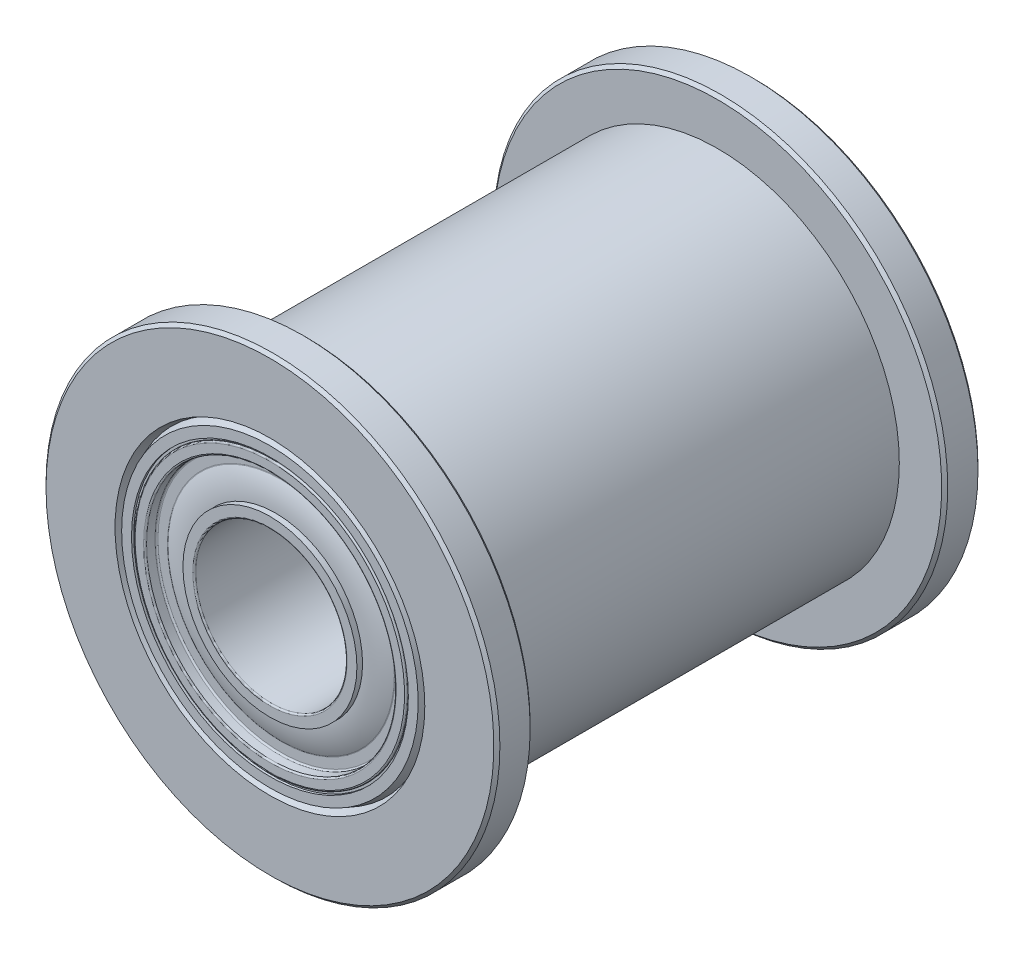
SolidWorks part; units mm, degrees
ref_plane "Front" through (0, 0, 0) normal (0, 0, 1) x (1, 0, 0)
ref_plane "Top" through (0, 0, 0) normal (0, 1, 0) x (1, 0, 0)
ref_plane "Right" through (0, 0, 0) normal (1, 0, 0) x (0, 0, -1)
sketch "Sketch1" plane through (0, 0, 0) normal (1, 0, 0) x (0, 0, -1)
  line L0 (-8, 0) -> (8, 0) construction
  line L1 (8, 7.5) -> (8, -7.5) construction
  line L2 (8, 7.5) -> (6.8, 7.5) construction
  line L3 (8, 2.5) -> (8, -2.5) construction
  line L4 (8, 6) -> (8, -6) construction
  line L5 (6, 0) -> (-6, 0) construction
  line L6 (6.8, 7.5) -> (6.8, 6) construction
  dimension "D3" = 1.2
  dimension "Width" = 16
  dimension "OD" = 15
  dimension "ID" = 5
  dimension "Diameter" = 12
  dimension "Max Belt Width" = 12
  dimension "Groove Depth" = 1.5
sketch "Sketch2" plane through (0, 0, 0) normal (1, 0, 0) x (0, 0, -1)
  line L0 (8, 2.5) -> (0, 2.5)
  line L1 (8, 2.5) -> (8, 2.875)
  line L2 (8, 7.5) -> (8, -7.5) construction
  line L3 (8, 2.875) -> (7.625, 2.875) construction
  line L4 (7.8125, 4.125) -> (7.8125, 2.875) construction
  line L5 (8, 4.5) -> (0, 4.5)
  line L6 (7.625, 3.75) -> (7.625, 4.125)
  line L7 (8, 4.5) -> (8, 4.125)
  line L8 (8, 4.125) -> (7.625, 4.125)
  line L9 (7.625, 4.125) -> (7.625, 2.875) construction
  line L10 (0, 4.5) -> (0, 2.5)
  line L11 (7.8125, 2.875) -> (8, 2.875)
  arc A0 (7.625, 3.75) -> (7.8125, 2.875) centre (5.6771, 2.875) cw
  dimension "D1" = 1.5
  dimension "D2" = 0.375
revolve "Revolve1" add sketch "Sketch2" angle 360 about L0
mirror "Mirror1" about plane through (0, 0, 0) normal (0, 0, 1) of bodies 108
sketch "Sketch3" plane through (0, 0, 0) normal (1, 0, 0) x (0, 0, -1)
  line L0 (6.8, 7.5) -> (8, 7.5)
  line L1 (8, 7.5) -> (8, 5.1184)
  line L2 (8, 7.5) -> (8, -7.5) construction
  line L3 (8, 5.1184) -> (7.7, 5.0092)
  line L4 (7.7, 5.0092) -> (8, 4.9)
  line L5 (8, 4.9) -> (8, 4.575)
  line L6 (7.925, 4.5) -> (7.925, 4.575)
  line L7 (8, 4.5) -> (-8, 4.5) construction
  line L8 (7.925, 4.575) -> (8, 4.575)
  line L9 (6.8, 7.5) -> (6.8, 6)
  line L10 (6.8, 6) -> (-6.8, 6)
  line L11 (0, 6) -> (0, 4.5) construction
  line L12 (-7.925, 4.5) -> (7.925, 4.5)
  line L13 (-6.8, 7.5) -> (-6.8, 6)
  line L14 (-7.925, 4.575) -> (-8, 4.575)
  line L15 (-7.925, 4.5) -> (-7.925, 4.575)
  line L16 (-8, 4.9) -> (-8, 4.575)
  line L17 (-7.7, 5.0092) -> (-8, 4.9)
  line L18 (-8, 5.1184) -> (-7.7, 5.0092)
  line L19 (-8, 7.5) -> (-8, 5.1184)
  line L20 (-6.8, 7.5) -> (-8, 7.5)
  line L21 (7.7, 5.0092) -> (8, 5.0092) construction
  line L22 (7.85, 5.0092) -> (7.85, 4.5) construction
  dimension "D1" = 40
  dimension "D2" = 0.3
  dimension "D3" = 0.075
  dimension "D4" = 0.4
revolve "Revolve2" add sketch "Sketch3" angle 360 about L0
sketch "Sketch4" plane through (0, 0, 0) normal (0, 0, 1) x (1, 0, 0)
  line L0 (-0.6, 6) -> (0.6, 6)
  line L1 (-0.6, 6) -> (-0.6, 5.4) construction
  line L2 (-0.6, 5.4) -> (0.6, 5.4) construction
  line L3 (0.6, 5.4) -> (0.6, 6) construction
  line L4 (0, 6) -> (0, 5.4) construction
  arc A0 (0.6, 6) -> (-0.6, 6) centre (0, 6) cw
  dimension "D1" = 0.6
  dimension "D3" = 1.2
extrude "Cut-Extrude1" [suppressed] cut sketch "Sketch4" against normal up to surface and the other way up to surface up to face at (6, 0, -6.8) other way up to face at (7.5, 0, 6.8)
fillet "Fillet1" [suppressed] radius 0.05
pattern_circular "CirPattern3" [suppressed] count 20 over 360 of bodies 114
chamfer "Chamfer1" distance 0.1 angle 45 4 edges at (7.5, 0, -8) (7.5, 0, -6.8) (7.5, 0, 6.8) (7.5, 0, 8)
fillet "Fillet2" radius 0.05 10 edges at (3.75, 0, 7.625) (4.125, 0, 7.625) (4.5, 0, 8) (4.125, 0, 8) (2.5, 0, 8) (2.5, 0, -8) (4.5, 0, -8) (3.75, 0, -7.625) (4.125, 0, -8) (2.875, 0, -8)
combine bodies "Combine1" operation type add bodies to combine 110 109
ref_axis "Center Axis 1" through (0, 0, -7.95) along (0, 0, 1)
ref_plane "Contact Plane 1" through (0, 0, -6) normal (0, 0, 1) x (1, 0, 0)
ref_plane "Contact Plane 2" through (0, 0, 6) normal (0, 0, 1) x (1, 0, 0)
equation "\"D1@Sketch4\"=\"Groove Depth@Sketch1\"/2.5"
equation "\"D3@Sketch4\"=\"Diameter@Sketch1\"/10"
equation "\"D2@Sketch3\"=\"D3@Sketch1\"/4"
equation "\"D1@Sketch2\"=(\"OD@Sketch1\"-\"Diameter@Sketch1\")/2"
equation "\"D2@Sketch2\"=\"D1@Sketch2\"/4"
equation "\"D3@Sketch3\"=\"D2@Sketch3\"/4"
equation "\"D4@Sketch3\"=\"D3@Sketch1\"/3"
